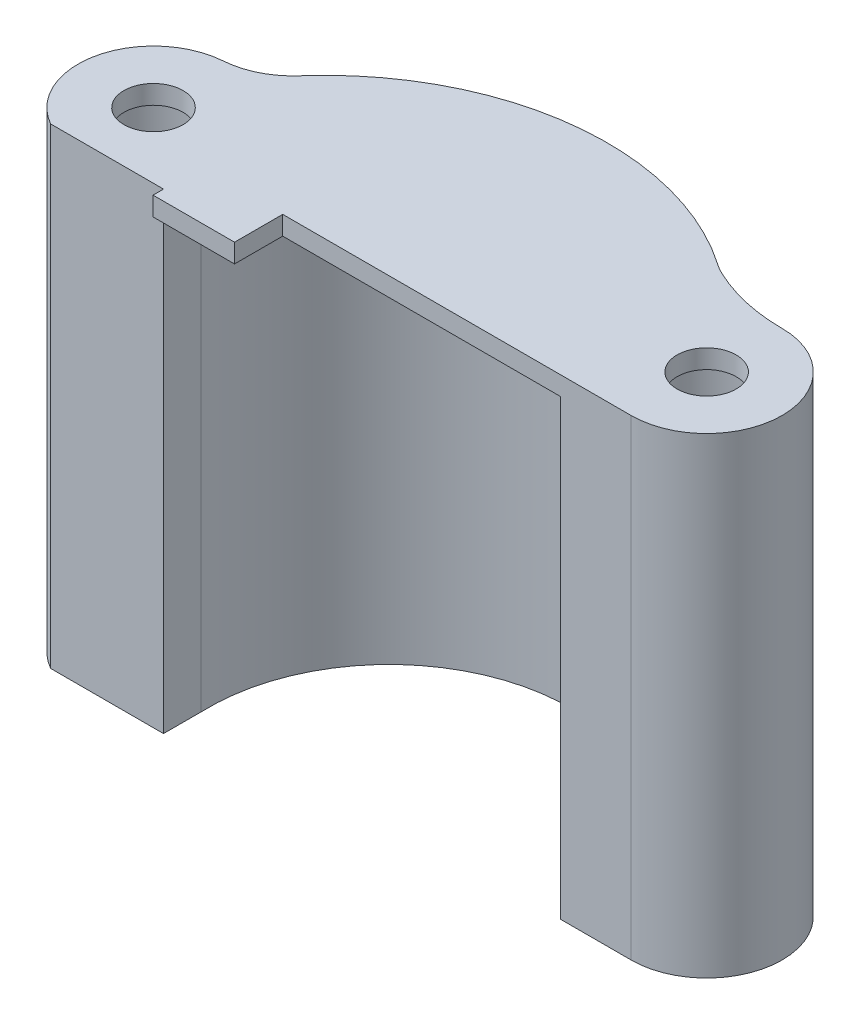
SolidWorks part; units mm, degrees
material "PLA/ABS"
ref_plane "Front Plane" through (0, 0, 0) normal (0, 0, 1) x (1, 0, 0)
ref_plane "Top Plane" through (0, 0, 0) normal (0, 1, 0) x (1, 0, 0)
ref_plane "Right Plane" through (0, 0, 0) normal (1, 0, 0) x (0, 0, -1)
other "Bounding Box"
ref_plane "Default Plane" through (-8.9266, -12.7485, 0) normal (-0.1736, 0.9848, 0) x (0.9848, 0.1736, 0)
sketch "Sketch1" plane through (0, 0, 0) normal (0, 1, 0) x (1, 0, 0)
  line B0 (-13.6378, -15.7405) -> (-16.8128, -15.7405) construction
  line B1 (16.6091, -12.5655) -> (19.7841, -12.5655) construction
  arc B2 (-13.6378, -15.7405) -> (16.6091, -12.5655) centre (1.591, -15.1567) cw
  arc B3 (-16.8128, -15.7405) -> (19.7841, -12.5655) centre (1.6704, -16.283) cw
sketch_block_instance "Cover for wepon motor-1"
sketch_block "Cover for wepon motor" parameters "D3"=15.24, "D4"=18.4912, "D1"=3.175, "D2"=3.175
sketch "Sketch2" plane through (0, 0, 0) normal (0, 1, 0) x (1, 0, 0)
  line L0 (-13.6378, -18.9155) -> (-13.6378, -15.7405)
  line L1 (16.6091, -12.5655) -> (16.6091, -15.7405)
  line L2 (-23.1387, -18.9155) -> (-13.6378, -18.9155)
  line L3 (16.6091, -15.7405) -> (22.5457, -15.7405)
  arc A1 (-13.6378, -15.7405) -> (16.6091, -12.5655) centre (1.591, -15.1567) cw
  circle A2 centre (-19.9967, -13.3973) radius 4.7625
  circle A3 centre (22.5457, -9.3905) radius 4.7625
  arc A5 (-19.9967, -7.0473) -> (-23.1387, -18.9155) centre (-19.9967, -13.3973) ccw
  arc A7 (22.5457, -15.7405) -> (22.5457, -3.0405) centre (22.5457, -9.3905) ccw
  arc A8 (-19.9967, -7.0473) -> (-17.6403, -6.7838) centre (-19.9399, 3.1125) ccw
  arc A9 (22.5457, -3.0405) -> (15.4926, -1.3102) centre (22.5457, 12.1995) cw
  arc A20 (-17.6403, -6.7838) -> (15.4926, -1.3102) centre (1.663, -20.6134) cw
  dimension "D1" = 9.525
  dimension "D2" = 15.24
  dimension "D7" = 1.5875
  dimension "D9" = 1.5875
  dimension "D10" = 10.16
  dimension "D11" = 15.24
  dimension "D4" = 3.175
extrude "Boss-Extrude1" add sketch "Sketch2" along normal blind 38.1 contours L0 A1 L1 | A7 A3 | A5 A2 region at (-18.3883, 0, 18.3207)
sketch "Sketch3" plane through (0, 38.1, 0) normal (0, 1, 0) x (-1, 0, 0)
  line L0 (13.6378, 15.7405) -> (3.5038, 15.7405)
  line L1 (3.5038, 15.7405) -> (3.5038, 12.5655)
  line L2 (3.5038, 12.5655) -> (-16.6091, 12.5655)
  line L3 (13.6378, 18.9155) -> (13.6378, 15.7405)
  line L4 (-16.6091, 12.5655) -> (-16.6091, 15.7405)
  line L5 (-16.6091, 15.7405) -> (-22.5457, 15.7405)
  line L6 (13.6378, 18.9155) -> (13.6378, 15.7405)
  line L7 (-16.6091, 12.5655) -> (-16.6091, 15.7405)
  line L8 (-16.6091, 15.7405) -> (-22.5457, 15.7405)
  line L13 (23.1387, 18.9155) -> (13.6378, 18.9155)
  line L14 (23.1387, 18.9155) -> (13.6378, 18.9155)
  circle A0 centre (-22.5457, 9.3905) radius 2.4892
  circle A2 centre (19.9967, 13.3973) radius 2.4892
  arc A9 (-15.4926, 1.3102) -> (17.6403, 6.7838) centre (-1.663, 20.6134) ccw
  arc A10 (-15.4926, 1.3102) -> (17.6403, 6.7838) centre (-1.663, 20.6134) ccw
  arc A11 (19.9967, 7.0473) -> (17.6403, 6.7838) centre (19.9399, -3.1125) ccw
  arc A12 (19.9967, 7.0473) -> (23.1387, 18.9155) centre (19.9967, 13.3973) ccw
  arc A13 (-16.6091, 12.5655) -> (13.6378, 15.7405) centre (-1.591, 15.1567) ccw
  arc A14 (-22.5457, 15.7405) -> (-22.5457, 3.0405) centre (-22.5457, 9.3905) ccw
  arc A15 (-15.4926, 1.3102) -> (-22.5457, 3.0405) centre (-22.5457, -12.1995) ccw
  arc A20 (19.9967, 7.0473) -> (17.6403, 6.7838) centre (19.9399, -3.1125) ccw
  arc A21 (19.9967, 7.0473) -> (23.1387, 18.9155) centre (19.9967, 13.3973) ccw
  arc A23 (-22.5457, 15.7405) -> (-22.5457, 3.0405) centre (-22.5457, 9.3905) ccw
  arc A24 (-15.4926, 1.3102) -> (-22.5457, 3.0405) centre (-22.5457, -12.1995) ccw
  dimension "D3" = 4.9784
  dimension "D2" = 3.175
  dimension "D4" = 20.1129
  dimension "D1" = 0
extrude "Boss-Extrude2" add sketch "Sketch3" along normal blind 1.5875
sketch "Sketch4" plane through (0, 39.6875, 0) normal (0, 1, 0) x (-1, 0, 0)
  line L0 (3.5038, 15.7405) -> (3.5038, 12.5655)
  line L1 (13.6378, 15.7405) -> (6.7798, 15.7405)
  line L2 (13.6378, 15.7405) -> (13.6378, 19.7971)
  line L3 (13.6378, 19.7971) -> (6.7798, 19.7971)
  line L4 (6.7798, 15.7405) -> (6.7798, 19.7971)
  line L5 (13.6378, 18.9155) -> (13.6378, 15.7405) construction
  line L7 (3.5038, 12.5655) -> (-16.6091, 12.5655)
  line L9 (6.7798, 15.7405) -> (-16.6091, 15.7405)
  line L10 (-16.6091, 12.5655) -> (-16.6091, 15.7405)
  line M10 (13.6378, 18.9155) -> (13.6378, 15.7405)
  line M11 (13.6378, 15.7405) -> (3.5038, 15.7405)
  line M12 (3.5038, 15.7405) -> (3.5038, 12.5655)
  line M13 (3.5038, 12.5655) -> (-16.6091, 12.5655)
  line M14 (-16.6091, 12.5655) -> (-16.6091, 15.7405)
  dimension "D1" = 6.858
  dimension "D2" = 4.0566
extrude "Boss-Extrude3" add sketch "Sketch4" against normal up to surface (1.5875 mm away) contours L9 M12 M14 M13 | L4 L3 M11 M10 region at (-10.2088, 39.6875, 17.7688) region at (6.5526, 39.6875, 14.153) up to face at (-1.3805, 38.1, 10.6147)
fillet "Fillet2" radius 6.35 2 edges at (15.4926, 19.8438, 1.3102) (-17.6403, 19.8438, 6.7838)
